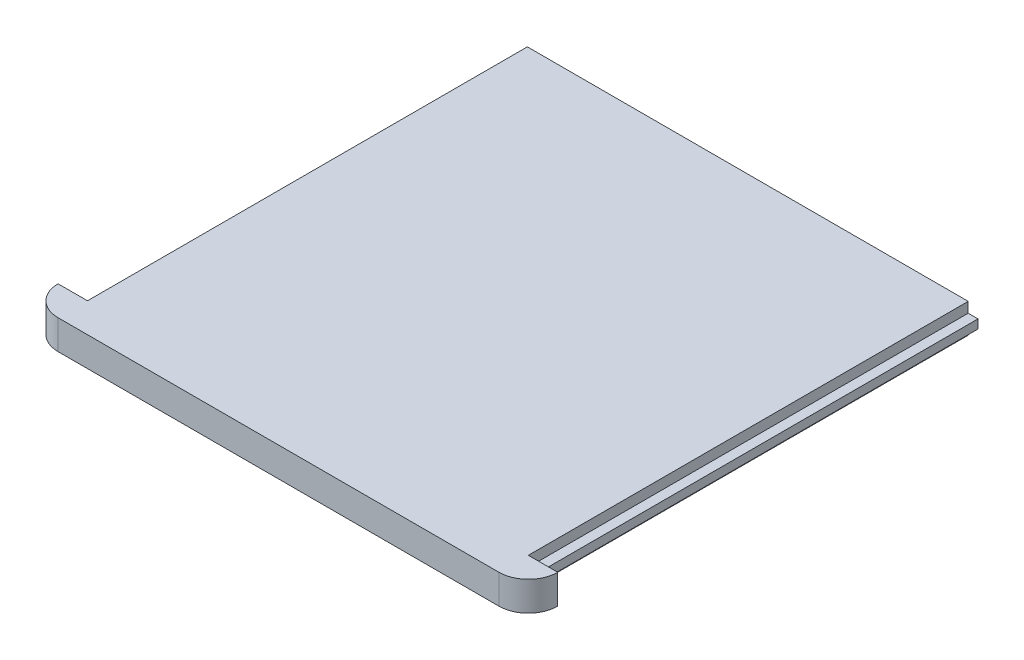
SolidWorks part; units mm, degrees
ref_plane "Front Plane" through (0, 0, 0) normal (0, 0, 1) x (1, 0, 0)
ref_plane "Top Plane" through (0, 0, 0) normal (0, 1, 0) x (1, 0, 0)
ref_plane "Right Plane" through (0, 0, 0) normal (1, 0, 0) x (0, 0, -1)
sketch "Sketch1" plane through (0, 0, 0) normal (0, 1, 0) x (1, 0, 0)
  line L1 (-22.5, 22.5) -> (22.5, 22.5)
  line L2 (-22.5, 22.5) -> (-22.5, -22.5)
  line L3 (-22.5, -22.5) -> (22.5, -22.5)
  line L4 (22.5, 22.5) -> (22.5, -22.5)
  line L5 (-22.5, 22.5) -> (22.5, -22.5) construction
  line L6 (-22.5, -22.5) -> (22.5, 22.5) construction
  point P0 (0, 0)
  dimension "D1" = 45
  dimension "D2" = 45
extrude "Boss-Extrude1" add sketch "Sketch1" along normal blind 3
sketch "Sketch29" plane through (22.5, 0, 0) normal (1, 0, 0) x (0, 0, -1)
  line L1 (-22.5, 3) -> (-22.5, 0) construction
  line L2 (-22.5, 1) -> (22.5, 1)
  line L3 (22.5, 3) -> (22.5, 0) construction
  line L4 (22.5, 1) -> (22.5, 2)
  line L5 (22.5, 2) -> (-22.5, 2)
  line L6 (-22.5, 2) -> (-22.5, 1)
extrude "Boss-Extrude2" add sketch "Sketch29" along normal blind 1
sketch "Sketch30" plane through (-22.5, 0, 0) normal (-1, 0, 0) x (0, 0, 1)
  line L1 (-22.5, 1) -> (22.5, 1)
  line L2 (22.5, 3) -> (22.5, 0) construction
  line L3 (22.5, 1) -> (22.5, 2)
  line L4 (22.5, 2) -> (-22.5, 2)
  line L5 (-22.5, 2) -> (-22.5, 1)
extrude "Boss-Extrude3" add sketch "Sketch30" along normal blind 1
sketch "Sketch31" plane through (0, 3, 0) normal (0, 1, 0) x (1, 0, 0)
  line L0 (-2, -22.5) -> (-2, -18.5)
  line L1 (-22.5, -22.5) -> (22.5, -22.5) construction
  line L2 (2, -22.5) -> (-2, -22.5)
  line L5 (-2, -18.5) -> (-6, -18.5)
  line L6 (-6, -18.5) -> (-6, -14.5)
  line L13 (-6, -14.5) -> (6, -14.5)
  line L14 (6, -14.5) -> (6, -18.5)
  line L15 (6, -18.5) -> (2, -18.5)
  line L16 (2, -18.5) -> (2, -22.5)
extrude "Cut-Extrude2" cut sketch "Sketch31" against normal blind 1.5
sketch "Sketch32" plane through (0, 0, 14.5) normal (0, 0, 1) x (1, 0, 0)
  line L0 (-6, 3) -> (-6, 1.5)
  line L1 (6, 1.5) -> (-6, 1.5) construction
  line L2 (-6, 1.5) -> (6, 1.5)
  line L3 (6, 1.5) -> (6, 3)
  line L4 (6, 3) -> (-6, 3)
extrude "Boss-Extrude4" add sketch "Sketch32" along normal blind 8
sketch "Sketch33" plane through (0, 0, 22.5) normal (0, 0, 1) x (1, 0, 0)
  line L0 (-22.5, 2) -> (-23.5, 2)
  line L1 (-23.5, 2) -> (-23.5, 1.95)
  line L2 (-23.5, 1) -> (-23.5, 2) construction
  line L3 (-23.5, 1.95) -> (-22.5, 1.95)
  line L4 (-22.5, 1.95) -> (-22.5, 2)
  line L5 (-22.5, 1) -> (-23.5, 1)
  line L6 (-23.5, 1) -> (-23.5, 1.05)
  line L7 (-23.5, 1.05) -> (-22.5, 1.05)
  line L8 (-22.5, 1.05) -> (-22.5, 1)
  line L9 (0, 0) -> (0, 6.3521) construction
  line L10 (22.5, 1.05) -> (22.5, 1)
  line L11 (23.5, 1.05) -> (22.5, 1.05)
  line L12 (23.5, 1) -> (23.5, 1.05)
  line L13 (22.5, 1) -> (23.5, 1)
  line L14 (22.5, 1.95) -> (22.5, 2)
  line L15 (23.5, 1.95) -> (22.5, 1.95)
  line L16 (23.5, 2) -> (23.5, 1.95)
  line L17 (22.5, 2) -> (23.5, 2)
extrude "Cut-Extrude3" cut sketch "Sketch33" against normal blind 86
sketch "Sketch34" plane through (0, 0, 22.5) normal (0, 0, 1) x (1, 0, 0)
  line L1 (-26.4757, 8.7422) -> (26.4757, 8.7422)
  line L2 (-26.4757, 8.7422) -> (-26.4757, -8.7422)
  line L3 (-26.4757, -8.7422) -> (26.4757, -8.7422)
  line L4 (26.4757, 8.7422) -> (26.4757, -8.7422)
  line L5 (-26.4757, 8.7422) -> (26.4757, -8.7422) construction
  line L6 (-26.4757, -8.7422) -> (26.4757, 8.7422) construction
  point P0 (0, 0)
extrude "Cut-Extrude4" cut sketch "Sketch34" against normal blind 0.1
sketch "Sketch35" plane through (0, 0, 22.4) normal (0, 0, 1) x (1, 0, 0)
  line L0 (-22.5, 3) -> (25.5, 3)
  line L1 (25.5, 3) -> (25.5, 0)
  line L2 (25.5, 0) -> (-25.5, 0)
  line L3 (-25.5, 0) -> (-25.5, 3)
  line L4 (-25.5, 3) -> (-22.5, 3)
extrude "Boss-Extrude5" add sketch "Sketch35" along normal blind 3
fillet "Fillet1" radius 3 2 edges at (25.5, 1.5, 25.4) (-25.5, 1.5, 25.4)
